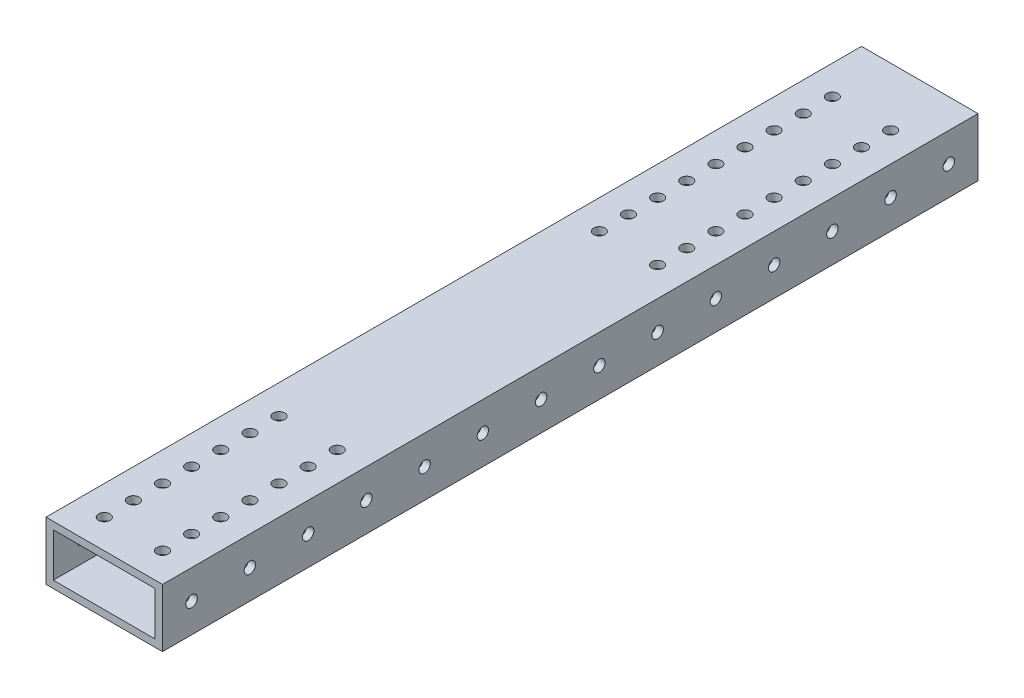
SolidWorks part; units mm, degrees
material "6061-T6 (SS)"
ref_plane "Front Plane" through (0, 0, 0) normal (0, 0, 1) x (1, 0, 0)
ref_plane "Top Plane" through (0, 0, 0) normal (0, 1, 0) x (1, 0, 0)
ref_plane "Right Plane" through (0, 0, 0) normal (1, 0, 0) x (0, 0, -1)
sketch "Sketch1" plane through (0, 0, 0) normal (0, 0, 1) x (1, 0, 0)
  line L0 (-22.225, 9.525) -> (22.225, 9.525)
  line L1 (-25.4, 12.7) -> (25.4, 12.7)
  line L2 (-25.4, 12.7) -> (-25.4, -12.7)
  line L3 (-25.4, -12.7) -> (25.4, -12.7)
  line L4 (25.4, 12.7) -> (25.4, -12.7)
  line L5 (22.225, 9.525) -> (22.225, -9.525)
  line L6 (-22.225, -9.525) -> (22.225, -9.525)
  line L7 (-22.225, 9.525) -> (-22.225, -9.525)
  line L8 (-25.4, 12.7) -> (25.4, -12.7) construction
  line L9 (25.4, 12.7) -> (-25.4, -12.7) construction
  point P5 (0, 0)
  dimension "D1" = 50.8
  dimension "D2" = 25.4
  dimension "D3" = 3.175
extrude "Boss-Extrude1" add sketch "Sketch1" along normal mid plane 355.6
sketch "Sketch2" plane through (0, 12.7, 0) normal (0, -1, 0) x (1, 0, 0)
  circle A36 centre (-12.7, 165.1) radius 2.4892 construction
  circle A37 centre (-12.7, 152.4) radius 2.4892 construction
  circle A38 centre (-12.7, 139.7) radius 2.4892 construction
  circle A39 centre (-12.7, 127) radius 2.4892 construction
  circle A40 centre (-12.7, 114.3) radius 2.4892 construction
  circle A41 centre (-12.7, 101.6) radius 2.4892 construction
  circle A42 centre (-12.7, 88.9) radius 2.4892 construction
  circle A50 centre (12.7, 165.1) radius 2.4892 construction
  circle A51 centre (12.7, 152.4) radius 2.4892 construction
  circle A52 centre (12.7, 139.7) radius 2.4892 construction
  circle A53 centre (12.7, 127) radius 2.4892 construction
  circle A54 centre (12.7, 114.3) radius 2.4892 construction
  circle A55 centre (12.7, 101.6) radius 2.4892 construction
  circle A56 centre (12.7, 88.9) radius 2.4892 construction
  circle A57 centre (-12.7, 165.1) radius 2.4892
  circle A58 centre (-12.7, 152.4) radius 2.4892
  circle A59 centre (-12.7, 139.7) radius 2.4892
  circle A60 centre (-12.7, 127) radius 2.4892
  circle A61 centre (-12.7, 114.3) radius 2.4892
  circle A62 centre (-12.7, 101.6) radius 2.4892
  circle A63 centre (-12.7, 88.9) radius 2.4892
  circle A71 centre (12.7, 165.1) radius 2.4892
  circle A72 centre (12.7, 152.4) radius 2.4892
  circle A73 centre (12.7, 139.7) radius 2.4892
  circle A74 centre (12.7, 127) radius 2.4892
  circle A75 centre (12.7, 114.3) radius 2.4892
  circle A76 centre (12.7, 101.6) radius 2.4892
  circle A77 centre (12.7, 88.9) radius 2.4892
extrude "Cut-Extrude1" cut sketch "Sketch2" along normal up to next
sketch "Sketch3" plane through (25.4, 0, 0) normal (1, 0, 0) x (0, 0, -1)
  line L0 (-177.8, 0) -> (177.8, 0) construction
  line L1 (-177.8, -12.7) -> (-177.8, 12.7) construction
  line L2 (177.8, -12.7) -> (177.8, 12.7) construction
  circle A0 centre (-165.1, 0) radius 2.4892
  circle A1 centre (-139.7, 0) radius 2.4892
  circle A2 centre (-114.3, 0) radius 2.4892
  circle A3 centre (-88.9, 0) radius 2.4892
  circle A4 centre (-63.5, 0) radius 2.4892
  circle A5 centre (-38.1, 0) radius 2.4892
  circle A6 centre (-12.7, 0) radius 2.4892
  circle A7 centre (12.7, 0) radius 2.4892
  circle A8 centre (38.1, 0) radius 2.4892
  circle A9 centre (63.5, 0) radius 2.4892
  circle A10 centre (88.9, 0) radius 2.4892
  circle A11 centre (114.3, 0) radius 2.4892
  circle A12 centre (139.7, 0) radius 2.4892
  circle A13 centre (165.1, 0) radius 2.4892
  dimension "D1" = 4.9784
  dimension "D2" = 12.7
  dimension "D4" = 25.4
  dimension "D3" = 14
extrude "Cut-Extrude2" cut sketch "Sketch3" against normal through all
sketch "Sketch4" plane through (0, -12.7, 0) normal (0, -1, 0) x (1, 0, 0)
  circle A0 centre (-12.7, -152.4) radius 2.4892 construction
  circle A1 centre (-12.7, -139.7) radius 2.4892 construction
  circle A2 centre (-12.7, -127) radius 2.4892 construction
  circle A3 centre (-12.7, -114.3) radius 2.4892 construction
  circle A4 centre (-12.7, -101.6) radius 2.4892 construction
  circle A5 centre (-12.7, -88.9) radius 2.4892 construction
  circle A6 centre (-12.7, -76.2) radius 2.4892 construction
  circle A7 centre (-12.7, -63.5) radius 2.4892 construction
  circle A8 centre (-12.7, -50.8) radius 2.4892 construction
  circle A9 centre (12.7, -50.8) radius 2.4892 construction
  circle A10 centre (12.7, -63.5) radius 2.4892 construction
  circle A11 centre (12.7, -76.2) radius 2.4892 construction
  circle A12 centre (12.7, -88.9) radius 2.4892 construction
  circle A13 centre (12.7, -101.6) radius 2.4892 construction
  circle A14 centre (12.7, -114.3) radius 2.4892 construction
  circle A15 centre (12.7, -127) radius 2.4892 construction
  circle A16 centre (12.7, -139.7) radius 2.4892 construction
  circle A17 centre (12.7, -152.4) radius 2.4892 construction
  circle A18 centre (-12.7, -152.4) radius 2.4892
  circle A19 centre (-12.7, -139.7) radius 2.4892
  circle A20 centre (-12.7, -127) radius 2.4892
  circle A21 centre (-12.7, -114.3) radius 2.4892
  circle A22 centre (-12.7, -101.6) radius 2.4892
  circle A23 centre (-12.7, -88.9) radius 2.4892
  circle A24 centre (-12.7, -76.2) radius 2.4892
  circle A25 centre (-12.7, -63.5) radius 2.4892
  circle A26 centre (-12.7, -50.8) radius 2.4892
  circle A27 centre (12.7, -50.8) radius 2.4892
  circle A28 centre (12.7, -63.5) radius 2.4892
  circle A29 centre (12.7, -76.2) radius 2.4892
  circle A30 centre (12.7, -88.9) radius 2.4892
  circle A31 centre (12.7, -101.6) radius 2.4892
  circle A32 centre (12.7, -114.3) radius 2.4892
  circle A33 centre (12.7, -127) radius 2.4892
  circle A34 centre (12.7, -139.7) radius 2.4892
  circle A35 centre (12.7, -152.4) radius 2.4892
extrude "Cut-Extrude3" cut sketch "Sketch4" against normal through all
